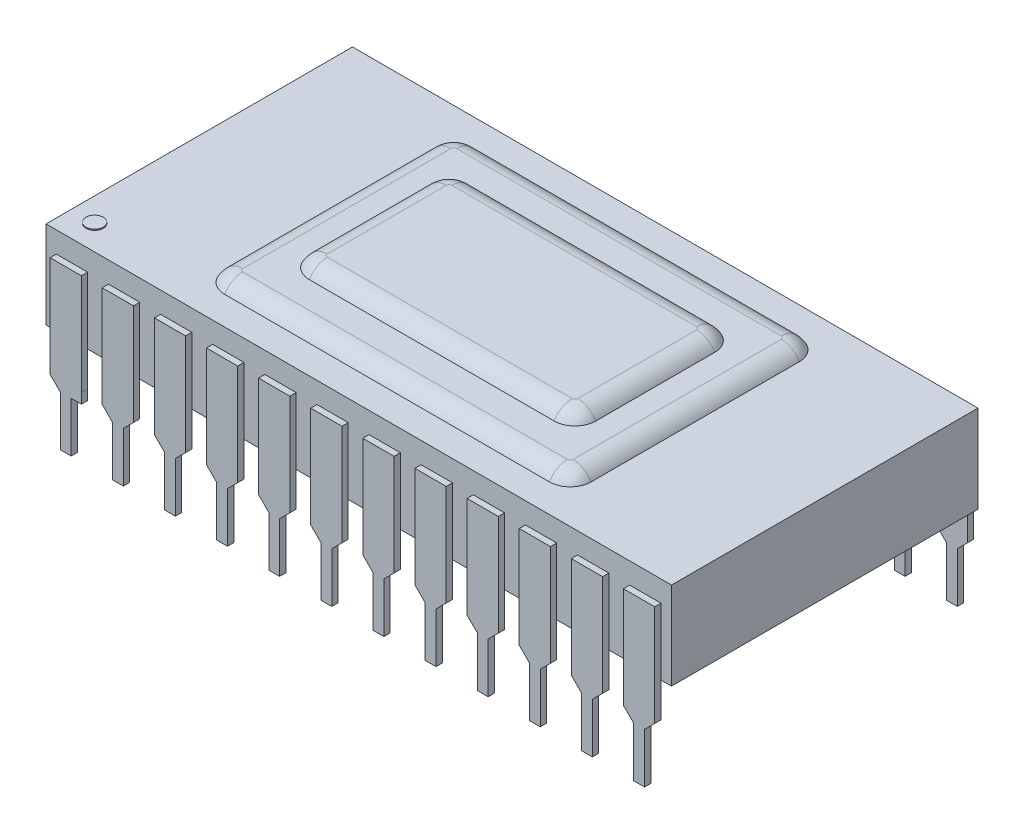
SolidWorks part; units mm, degrees
ref_plane "Спереди" through (0, 0, 0) normal (0, 0, 1) x (1, 0, 0)
ref_plane "Сверху" through (0, 0, 0) normal (0, 1, 0) x (1, 0, 0)
ref_plane "Справа" through (0, 0, 0) normal (1, 0, 0) x (0, 0, -1)
sketch "Эскиз1" plane through (0, 0, 0) normal (0, 1, 0) x (1, 0, 0)
  line L1 (0, 0) -> (30, 0)
  line L2 (0, 0) -> (0, -7.35)
  line L3 (0, -7.35) -> (30, -7.35)
  line L4 (30, 0) -> (30, -7.35)
  dimension "D1" = 30
  dimension "D2" = 7.35
extrude "Бобышка-Вытянуть1" add sketch "Эскиз1" along normal blind 4.2
sketch "Эскиз3" plane through (0, 0, 7.35) normal (0, 0, 1) x (1, 0, 0)
  line L0 (1.9953, 3.1943) -> (1.9953, -1.6519)
  line L1 (1.2453, 3.1943) -> (1.2453, -4.5382) construction
  line L2 (3.7453, 3.1943) -> (3.7453, -4.5382) construction
  line L3 (2.9953, -1.6519) -> (3.4853, -2.1419)
  line L4 (2.9953, 3.1943) -> (2.9953, -1.6519)
  line L5 (3.4853, -2.1419) -> (3.4853, -4.5382)
  line L6 (1.9953, -1.6519) -> (1.9936, -1.6536)
  line L7 (1.9953, 3.1943) -> (0.4953, 3.1943)
  line L8 (0.4953, 3.1943) -> (0.4953, -1.6519)
  line L9 (0.4953, -1.6519) -> (0.9853, -2.1419)
  line L10 (0.9853, -2.1419) -> (0.9853, -4.5382)
  line L11 (1.5053, -2.1419) -> (1.5053, -4.5382)
  line L12 (4.0053, -2.1419) -> (4.0053, -4.5382)
  line L13 (4.4953, -1.6519) -> (4.0053, -2.1419)
  line L14 (4.4953, 3.1943) -> (4.4953, -1.6519)
  line L15 (4.4953, 3.1943) -> (2.9953, 3.1943)
  line L16 (4.0053, -4.5382) -> (3.4853, -4.5382)
  line L17 (6.2453, 3.1943) -> (6.2453, -4.5382) construction
  line L18 (5.4953, -1.6519) -> (5.9853, -2.1419)
  line L19 (5.4953, 3.1943) -> (5.4953, -1.6519)
  line L20 (5.9853, -2.1419) -> (5.9853, -4.5382)
  line L21 (6.5053, -2.1419) -> (6.5053, -4.5382)
  line L22 (6.9953, -1.6519) -> (6.5053, -2.1419)
  line L23 (6.9953, 3.1943) -> (6.9953, -1.6519)
  line L24 (6.9953, 3.1943) -> (5.4953, 3.1943)
  line L25 (6.5053, -4.5382) -> (5.9853, -4.5382)
  line L26 (8.7453, 3.1943) -> (8.7453, -4.5382) construction
  line L27 (7.9953, -1.6519) -> (8.4853, -2.1419)
  line L28 (7.9953, 3.1943) -> (7.9953, -1.6519)
  line L29 (8.4853, -2.1419) -> (8.4853, -4.5382)
  line L30 (9.0053, -2.1419) -> (9.0053, -4.5382)
  line L31 (1.5053, -4.5382) -> (0.9853, -4.5382)
  line L32 (9.4953, -1.6519) -> (9.0053, -2.1419)
  line L33 (9.4953, 3.1943) -> (9.4953, -1.6519)
  line L34 (9.4953, 3.1943) -> (7.9953, 3.1943)
  line L35 (9.0053, -4.5382) -> (8.4853, -4.5382)
  line L36 (11.2453, 3.1943) -> (11.2453, -4.5382) construction
  line L37 (10.4953, -1.6519) -> (10.9853, -2.1419)
  line L38 (10.4953, 3.1943) -> (10.4953, -1.6519)
  line L39 (10.9853, -2.1419) -> (10.9853, -4.5382)
  line L40 (11.5053, -2.1419) -> (11.5053, -4.5382)
  line L41 (11.9953, -1.6519) -> (11.5053, -2.1419)
  line L42 (11.9953, 3.1943) -> (11.9953, -1.6519)
  line L43 (11.9953, 3.1943) -> (10.4953, 3.1943)
  line L44 (11.5053, -4.5382) -> (10.9853, -4.5382)
  line L45 (13.7453, 3.1943) -> (13.7453, -4.5382) construction
  line L46 (12.9953, -1.6519) -> (13.4853, -2.1419)
  line L47 (12.9953, 3.1943) -> (12.9953, -1.6519)
  line L48 (13.4853, -2.1419) -> (13.4853, -4.5382)
  line L49 (14.0053, -2.1419) -> (14.0053, -4.5382)
  line L50 (14.4953, -1.6519) -> (14.0053, -2.1419)
  line L51 (14.4953, 3.1943) -> (14.4953, -1.6519)
  line L52 (14.4953, 3.1943) -> (12.9953, 3.1943)
  line L53 (14.0053, -4.5382) -> (13.4853, -4.5382)
  line L54 (16.2453, 3.1943) -> (16.2453, -4.5382) construction
  line L55 (15.4953, -1.6519) -> (15.9853, -2.1419)
  line L56 (15.4953, 3.1943) -> (15.4953, -1.6519)
  line L57 (15.9853, -2.1419) -> (15.9853, -4.5382)
  line L58 (16.5053, -2.1419) -> (16.5053, -4.5382)
  line L59 (16.9953, -1.6519) -> (16.5053, -2.1419)
  line L60 (16.9953, 3.1943) -> (16.9953, -1.6519)
  line L61 (16.9953, 3.1943) -> (15.4953, 3.1943)
  line L62 (16.5053, -4.5382) -> (15.9853, -4.5382)
  line L63 (18.7453, 3.1943) -> (18.7453, -4.5382) construction
  line L64 (17.9953, -1.6519) -> (18.4853, -2.1419)
  line L65 (17.9953, 3.1943) -> (17.9953, -1.6519)
  line L66 (18.4853, -2.1419) -> (18.4853, -4.5382)
  line L67 (19.0053, -2.1419) -> (19.0053, -4.5382)
  line L68 (19.4953, -1.6519) -> (19.0053, -2.1419)
  line L69 (19.4953, 3.1943) -> (19.4953, -1.6519)
  line L70 (19.4953, 3.1943) -> (17.9953, 3.1943)
  line L71 (19.0053, -4.5382) -> (18.4853, -4.5382)
  line L72 (21.2453, 3.1943) -> (21.2453, -4.5382) construction
  line L73 (20.4953, -1.6519) -> (20.9853, -2.1419)
  line L74 (20.4953, 3.1943) -> (20.4953, -1.6519)
  line L75 (20.9853, -2.1419) -> (20.9853, -4.5382)
  line L76 (21.5053, -2.1419) -> (21.5053, -4.5382)
  line L77 (21.9953, -1.6519) -> (21.5053, -2.1419)
  line L78 (21.9953, 3.1943) -> (21.9953, -1.6519)
  line L79 (21.9953, 3.1943) -> (20.4953, 3.1943)
  line L80 (21.5053, -4.5382) -> (20.9853, -4.5382)
  line L81 (23.7453, 3.1943) -> (23.7453, -4.5382) construction
  line L82 (22.9953, -1.6519) -> (23.4853, -2.1419)
  line L83 (22.9953, 3.1943) -> (22.9953, -1.6519)
  line L84 (23.4853, -2.1419) -> (23.4853, -4.5382)
  line L85 (24.0053, -2.1419) -> (24.0053, -4.5382)
  line L86 (24.4953, -1.6519) -> (24.0053, -2.1419)
  line L87 (24.4953, 3.1943) -> (24.4953, -1.6519)
  line L88 (24.4953, 3.1943) -> (22.9953, 3.1943)
  line L89 (24.0053, -4.5382) -> (23.4853, -4.5382)
  line L90 (26.2453, 3.1943) -> (26.2453, -4.5382) construction
  line L91 (25.4953, -1.6519) -> (25.9853, -2.1419)
  line L92 (25.4953, 3.1943) -> (25.4953, -1.6519)
  line L93 (25.9853, -2.1419) -> (25.9853, -4.5382)
  line L94 (26.5053, -2.1419) -> (26.5053, -4.5382)
  line L95 (26.9953, -1.6519) -> (26.5053, -2.1419)
  line L96 (26.9953, 3.1943) -> (26.9953, -1.6519)
  line L97 (26.9953, 3.1943) -> (25.4953, 3.1943)
  line L98 (26.5053, -4.5382) -> (25.9853, -4.5382)
  line L99 (28.7453, 3.1943) -> (28.7453, -4.5382) construction
  line L100 (27.9953, -1.6519) -> (28.4853, -2.1419)
  line L101 (27.9953, 3.1943) -> (27.9953, -1.6519)
  line L102 (28.4853, -2.1419) -> (28.4853, -4.5382)
  line L103 (29.0053, -2.1419) -> (29.0053, -4.5382)
  line L104 (29.4953, -1.6519) -> (29.0053, -2.1419)
  line L105 (29.4953, 3.1943) -> (29.4953, -1.6519)
  line L106 (29.4953, 3.1943) -> (27.9953, 3.1943)
  line L107 (29.0053, -4.5382) -> (28.4853, -4.5382)
  line L109 (1.5053, -2.1419) -> (1.9936, -2.1419)
  line L110 (1.9936, -2.1419) -> (1.9936, -1.6536)
extrude "Бобышка-Вытянуть2" add sketch "Эскиз3" along normal blind 0.3
mirror "Зеркальное отражение1" of "Бобышка-Вытянуть2", "Бобышка-Вытянуть1"
sketch "Эскиз4" plane through (0, 4.2, 0) normal (0, 1, 0) x (1, 0, 0)
  line L0 (0, 7.35) -> (30, -7.35) construction
  line L1 (30, 7.35) -> (0, -7.35) construction
  line L3 (7.2106, 5.9928) -> (22.7894, 5.9928)
  line L4 (6.2106, 4.9928) -> (6.2106, -4.9928)
  line L5 (7.2106, -5.9928) -> (22.7894, -5.9928)
  line L6 (23.7894, 4.9928) -> (23.7894, -4.9928)
  line L7 (6.2106, 5.9928) -> (23.7894, -5.9928) construction
  line L8 (6.2106, -5.9928) -> (23.7894, 5.9928) construction
  arc A0 (7.2106, -5.9928) -> (6.2106, -4.9928) centre (7.2106, -4.9928) cw
  arc A1 (22.7894, -5.9928) -> (23.7894, -4.9928) centre (22.7894, -4.9928) ccw
  arc A2 (23.7894, 4.9928) -> (22.7894, 5.9928) centre (22.7894, 4.9928) ccw
  arc A3 (6.2106, 4.9928) -> (7.2106, 5.9928) centre (7.2106, 4.9928) cw
  point P8 (15, 0)
  dimension "D1" = 1
extrude "Бобышка-Вытянуть3" add sketch "Эскиз4" along normal blind 0.5
sketch "Эскиз5" plane through (0, 4.7, 0) normal (0, 1, 0) x (1, 0, 0)
  line L0 (0, 7.35) -> (30, -7.35) construction
  line L1 (30, -7.35) -> (30, 7.35) construction
  line L2 (30, 7.35) -> (0, -7.35) construction
  line L4 (9.1283, 3.8514) -> (20.8717, 3.8514)
  line L5 (8.1283, 2.8514) -> (8.1283, -2.8514)
  line L6 (9.1283, -3.8514) -> (20.8717, -3.8514)
  line L7 (21.8717, 2.8514) -> (21.8717, -2.8514)
  line L8 (8.1283, 3.8514) -> (21.8717, -3.8514) construction
  line L9 (8.1283, -3.8514) -> (21.8717, 3.8514) construction
  arc A0 (9.1283, -3.8514) -> (8.1283, -2.8514) centre (9.1283, -2.8514) cw
  arc A1 (20.8717, -3.8514) -> (21.8717, -2.8514) centre (20.8717, -2.8514) ccw
  arc A2 (21.8717, 2.8514) -> (20.8717, 3.8514) centre (20.8717, 2.8514) ccw
  arc A3 (9.1283, 3.8514) -> (8.1283, 2.8514) centre (9.1283, 2.8514) ccw
  point P4 (15, 0)
  dimension "D1" = 1
extrude "Бобышка-Вытянуть4" add sketch "Эскиз5" along normal blind 0.5
fillet "Скругление1" radius 1 8 edges at (8.4212, 5.2, 3.5585) (8.1283, 5.2, 0) (8.4212, 5.2, -3.5585) (15, 5.2, -3.8514) (21.5788, 5.2, -3.5585) (21.8717, 5.2, 0) (21.5788, 5.2, 3.5585) (15, 5.2, 3.8514)
sketch "Эскиз6" plane through (0, 5.2, 0) normal (0, 1, 0) x (1, 0, 0)
  text T0 "2120.24-11" font "Arial" height in points 4
sketch "Эскиз7" plane through (0, 4.2, 0) normal (0, 1, 0) x (1, 0, 0)
  circle A0 centre (1.1432, -6.1623) radius 0.4144
extrude "Бобышка-Вытянуть5" add sketch "Эскиз7" along normal blind 0.05
fillet "Скругление2" radius 1 8 edges at (6.5035, 4.7, 5.6999) (6.2106, 4.7, 0) (6.5035, 4.7, -5.6999) (15, 4.7, -5.9928) (23.4965, 4.7, -5.6999) (23.7894, 4.7, 0) (23.4965, 4.7, 5.6999) (15, 4.7, 5.9928)
